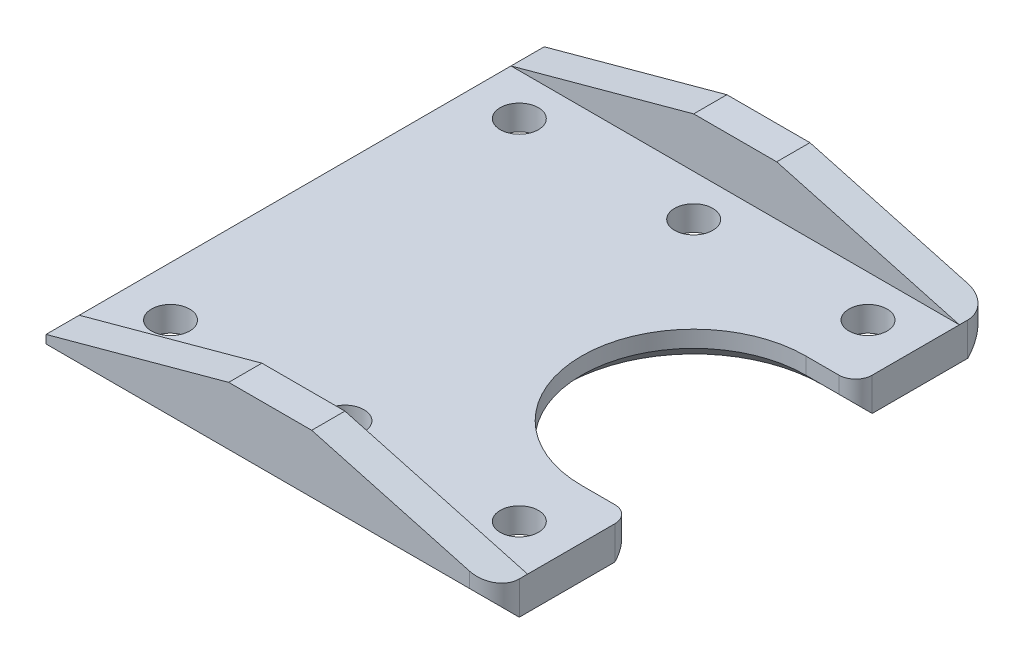
SolidWorks part; units mm, degrees
material "ABS"
ref_plane "正面" through (0, 0, 0) normal (0, 0, 1) x (1, 0, 0)
ref_plane "平面" through (0, 0, 0) normal (0, 1, 0) x (1, 0, 0)
ref_plane "右側面" through (0, 0, 0) normal (1, 0, 0) x (0, 0, -1)
sketch "ｽｹｯﾁ1" plane through (0, 0, 0) normal (1, 0, 0) x (0, 0, -1)
  line L0 (-15, 0) -> (15, 0)
  line L1 (15, 0) -> (15, 5)
  line L2 (15, 5) -> (13, 5)
  line L3 (13, 5) -> (13, 2)
  line L4 (13, 2) -> (-13, 2)
  line L5 (-13, 2) -> (-13, 5)
  line L6 (-13, 5) -> (-15, 5)
  line L7 (-15, 5) -> (-15, 0)
  point P8 (0, 0)
  dimension "D1" = 0
  dimension "D2" = 30
  dimension "D3" = 2
  dimension "D4" = 2
  dimension "D5" = 3
  dimension "D6" = 2
extrude "ﾎﾞｽ - 押し出し1" add sketch "ｽｹｯﾁ1" along normal mid plane 54
sketch "ｽｹｯﾁ2" plane through (0, 2, 0) normal (0, 1, 0) x (1, 0, 0)
  line L0 (24, 6.75) -> (28, 6.75)
  line L1 (28, 6.75) -> (28, -6.75)
  line L2 (28, -6.75) -> (24, -6.75)
  arc A0 (24, 6.75) -> (24, -6.75) centre (24, 0) ccw
  dimension "D1" = 13.5
  dimension "D2" = 24
  dimension "D3" = 0
  dimension "D4" = 4
extrude "ｶｯﾄ - 押し出し1" cut sketch "ｽｹｯﾁ2" against normal up to next
hole_wizard "M2 丸平ねじ用座ぐり穴1" positions "ｽｹｯﾁ3" profile "ｽｹｯﾁ4" counterbore size "M2" standard "JIS" end condition up to next
sketch "ｽｹｯﾁ3" plane through (0, 0, 0) normal (0, -1, 0) x (-1, 0, 0)
  line L0 (-27, -15) -> (27, -15) construction
  arc A0 (-24, -6.75) -> (-24, 6.75) centre (-24, 0) ccw construction
  point P0 (-24, -10.5)
  dimension "D1" = 4.5
  dimension "D2" = 0
sketch "ｽｹｯﾁ4" plane through (24, 0, 10.5) normal (1, 0, 0) x (0, 0, -1)
  line L0 (0, 0) -> (0, 2)
  line L1 (0, 2) -> (1.15, 2)
  line L3 (1.15, 2) -> (1.15, 0.5)
  line L4 (1.15, 0.5) -> (1.9, 0.5)
  line L5 (1.9, 0.5) -> (1.9, 0)
  line L7 (1.9, 0) -> (0, 0)
  line L11 (0, -6.35) -> (0, 107.95) construction
  dimension "通し穴の直径" = 2.3
  dimension "通し穴の深さ" = 2
  dimension "座ぐり穴の直径" = 3.8
  dimension "座ぐり穴の深さ" = 0.5
pattern_linear "直線ﾊﾟﾀｰﾝ1" count 3 spacing 10.5 along (-1, 0, 0) of "M2 丸平ねじ用座ぐり穴1"
mirror "ﾐﾗｰ1" about plane through (0, 0, 0) normal (0, 0, 1) of "直線ﾊﾟﾀｰﾝ1", "M2 丸平ねじ用座ぐり穴1"
chamfer "面取り1" distance 1 angle 45 3 edges at (25.5, 0, 6.75) (25.5, 0, -6.75) (17.25, 0, 0) tangent propagation no
mirror "ﾐﾗｰ3" about plane through (0, 0, 0) normal (1, 0, 0) of "面取り1", "ﾐﾗｰ1", "直線ﾊﾟﾀｰﾝ1", "M2 丸平ねじ用座ぐり穴1", "ｶｯﾄ - 押し出し1"
fillet "ﾌｨﾚｯﾄ1" radius 1.5 4 edges at (27, 2.5, -15) (27, 2.5, 15) (-27, 2.5, -15) (-27, 2.5, 15)
fillet "ﾌｨﾚｯﾄ2" radius 1 4 edges at (27, 1.5, -6.75) (27, 1.5, 6.75) (-27, 1.5, -6.75) (-27, 1.5, 6.75)
chamfer "面取り2" distance 1.5 angle 45 2 edges at (0, 0, -15) (0, 0, 15) tangent propagation no
sketch "ｽｹｯﾁ6" plane through (0, 0, 15) normal (0, 0, 1) x (1, 0, 0)
  line L0 (-27, 5) -> (11, 5)
  line L1 (25.5, 5) -> (-25.5, 5) construction
  line L2 (11, 5) -> (0, 2)
  line L3 (0, 2) -> (0, 0)
  line L4 (27, 0) -> (-27, 0) construction
  line L5 (0, 0) -> (-27, 0)
  line L6 (-27, 0) -> (-27, 5)
  line L8 (11, 5) -> (16, 5)
  line L9 (16, 5) -> (27, 2)
  line L10 (27, 2) -> (27, 5)
  line L11 (27, 5) -> (16, 5)
  line L12 (0, 2) -> (27, 2) construction
  line M5 (-25.5, 5) -> (-25.5, 1.5)
  line M6 (-25.5, 1.5) -> (25.5, 1.5)
  line M7 (25.5, 1.5) -> (25.5, 5)
  line M8 (25.5, 5) -> (-25.5, 5)
  dimension "D1" = 27
  dimension "D2" = 2
  dimension "D3" = 5
extrude "ｶｯﾄ - 押し出し2" cut sketch "ｽｹｯﾁ6" against normal through all contours L3 L2 M8 M5 M6 | L9 M8 M7 | L6 L5 L3 L0 M6 M5 | L9 L10 L11 region at (-14.9631, 1.0369, 15) region at (-10.1885, 3.367, 15) region at (22.3333, 4.1364, 15)
